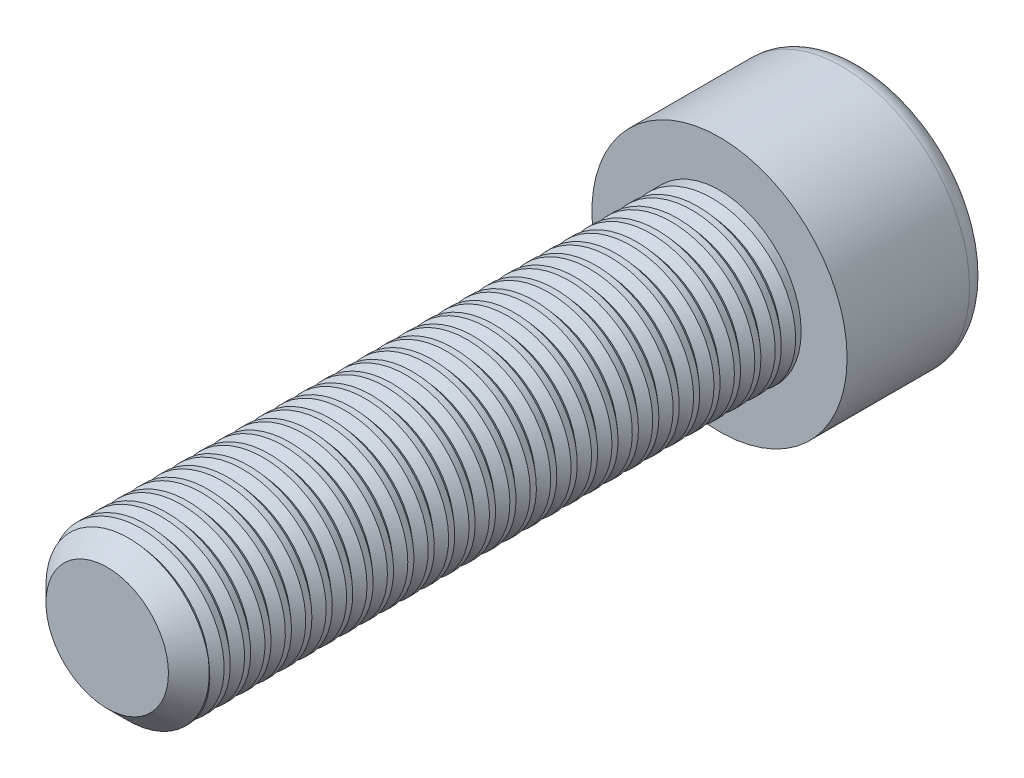
SolidWorks part; units mm, degrees
ref_plane "前视基准面" through (0, 0, 0) normal (0, 0, 1) x (1, 0, 0)
ref_plane "上视基准面" through (0, 0, 0) normal (0, 1, 0) x (1, 0, 0)
ref_plane "右视基准面" through (0, 0, 0) normal (1, 0, 0) x (0, 0, -1)
sketch "草图1" plane through (0, 0, 0) normal (0, 0, 1) x (1, 0, 0)
  circle A0 centre (0, 0) radius 6.25
  dimension "D1" = 12.5
extrude "凸台-拉伸1" add sketch "草图1" along normal blind 7
sketch "草图2" plane through (0, 0, 7) normal (0, 0, 1) x (1, 0, 0)
  circle A0 centre (0, 0) radius 4
  dimension "D1" = 8
extrude "凸台-拉伸2" add sketch "草图2" along normal blind 30
chamfer "倒角1" distance 1 angle 45 1 edges at (4, 0, 37)
sketch "草图3" plane through (0, 0, 37) normal (0, 0, 1) x (1, 0, 0)
  circle A0 centre (0, 0) radius 4
curve "螺旋线/涡状线1" pitch 1 height 30 turns 30
sketch "草图4" plane through (0, 0, 0) normal (0, 1, 0) x (1, 0, 0)
  line L0 (-4, -36.475) -> (-4, -35.775)
  line L1 (-4, -36.125) -> (-3.6, -36.125) construction
  line L2 (-4, -36.475) -> (-3.6, -36.125)
  line L3 (-3.6, -36.125) -> (-4, -35.775)
  dimension "D1" = 0.7
  dimension "D2" = 0.4
sweep "切除-扫描1" cut profiles "草图4" path "螺旋线/涡状线1"
sketch "草图5" plane through (0, 0, 0) normal (0, 0, -1) x (-1, 0, 0)
  line L1 (2.3996, 2.4984) -> (-0.9638, 3.3273)
  line L2 (-0.9638, 3.3273) -> (-3.3635, 0.8289)
  line L3 (-3.3635, 0.8289) -> (-2.3996, -2.4984)
  line L4 (-2.3996, -2.4984) -> (0.9638, -3.3273)
  line L5 (0.9638, -3.3273) -> (3.3635, -0.8289)
  line L6 (3.3635, -0.8289) -> (2.3996, 2.4984)
  circle A0 centre (0, 0) radius 3 construction
  dimension "D1" = 6
extrude "切除-拉伸1" cut sketch "草图5" against normal blind 3
fillet "圆角1" radius 1 1 edges at (6.25, 0, 0)
